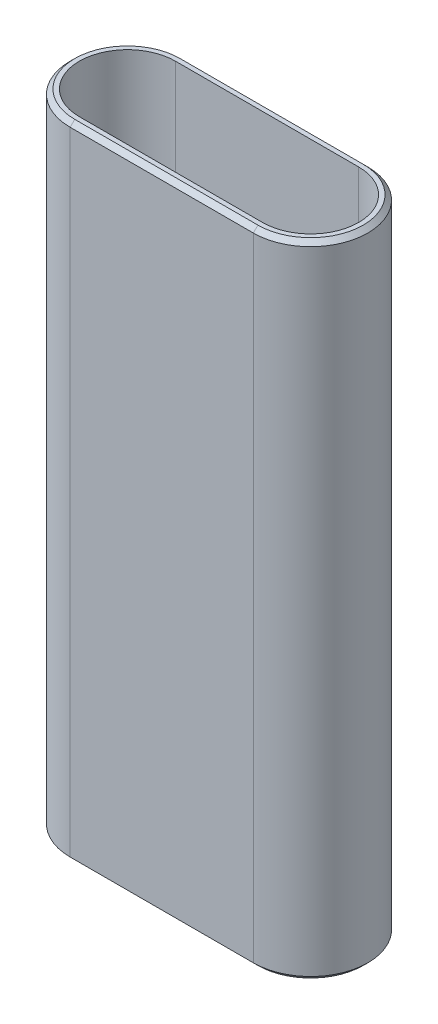
SolidWorks part; units mm, degrees
ref_plane "Front Plane" through (0, 0, 0) normal (0, 0, 1) x (1, 0, 0)
ref_plane "Top Plane" through (0, 0, 0) normal (0, 1, 0) x (1, 0, 0)
ref_plane "Right Plane" through (0, 0, 0) normal (1, 0, 0) x (0, 0, -1)
sketch "Sketch2" plane through (0, 12, 0) normal (0, -1, 0) x (1, 0, 0)
  line L8 (5.45, 3.45) -> (5.45, -3.45) construction
  line L9 (-7.45, -5.85) -> (7.45, -5.85)
  line L10 (-7.45, -5.85) -> (-7.45, 5.85)
  line L11 (-7.45, 5.85) -> (7.45, 5.85)
  line L12 (4.35, -3.85) -> (4.35, 3.85)
  line L13 (4.35, 3.85) -> (-4.35, 3.85)
  line L14 (-4.35, 3.85) -> (-4.35, -3.85)
  line L15 (-4.35, -3.85) -> (4.35, -3.85)
  line L16 (4.35, -3.85) -> (4.35, 3.85)
  line L17 (4.35, 3.85) -> (-4.35, 3.85)
  line L18 (-4.35, 3.85) -> (-4.35, -3.85)
  line L19 (-4.35, -3.85) -> (4.35, -3.85)
  line L20 (7.45, -5.85) -> (7.45, 5.85)
  line L21 (0, 5.85) -> (0, -5.85) construction
  line L22 (-7.45, 0) -> (7.45, 0) construction
  point P0 (0, 0)
  dimension "D2" = 2
  dimension "D3" = 2
  dimension "D1" = 0.4
extrude "Boss-Extrude1" add sketch "Sketch2" along normal offset from surface (12.6 mm away) 0.6 offset beyond the face yes
sketch "Sketch4" plane through (0, 0, 0) normal (1, 0, 0) x (0, 0, -1)
  line L1 (-1.6, 9.8) -> (-1.6, 8) construction
  line L2 (1.6, 8) -> (1.6, 9.8) construction
  line L3 (2.75, 8) -> (1.6, 8) construction
  line L4 (-1.6, 8) -> (-2.75, 8) construction
  line L5 (-2.75, 8) -> (-2.75, 12) construction
  line L6 (-2.75, 12) -> (-3.45, 12) construction
  line L7 (-3.45, 12) -> (-3.45, 0) construction
  line L8 (-3.45, 0) -> (3.45, 0) construction
  line L9 (3.45, 0) -> (3.45, 12) construction
  line L10 (3.45, 12) -> (2.75, 12) construction
  line L11 (2.75, 12) -> (2.75, 8) construction
  line L13 (-1.6, 9.8) -> (-1.6, 8) construction
  line L14 (1.6, 8) -> (1.6, 9.8) construction
  line L15 (2.75, 8) -> (1.6, 8) construction
  line L16 (-1.6, 8) -> (-2.75, 8) construction
  line L17 (-2.75, 8) -> (-2.75, 12) construction
  line L18 (-2.75, 12) -> (-3.45, 12) construction
  line L19 (-3.45, 12) -> (-3.45, 0) construction
  line L20 (-3.45, 0) -> (3.45, 0) construction
  line L21 (3.45, 0) -> (3.45, 12) construction
  line L22 (3.45, 12) -> (2.75, 12) construction
  line L23 (2.75, 12) -> (2.75, 8) construction
  line L24 (0, -990) -> (0, 49010) construction
  line L25 (-2.3, 10.25) -> (2.3, 10.25)
  line L26 (-2.3, 10.25) -> (-2.3, 7)
  line L27 (-2.3, 7) -> (2.3, 7)
  line L28 (1.6, 10) -> (-1.6, 10)
  line L29 (-1.6, 10) -> (-1.6, 9.8)
  line L30 (-1.6, 9.8) -> (1.6, 9.8)
  line L31 (1.6, 9.8) -> (1.6, 10)
  line L32 (1.6, 10) -> (-1.6, 10) construction
  line L33 (-1.6, 10) -> (-1.6, 9.8) construction
  line L34 (2.3, 10.25) -> (2.3, 7)
  line L35 (1.6, 9.8) -> (1.6, 10) construction
  point P20 (0, 10)
  dimension "D2" = 0.7
  dimension "D3" = 0.5
  dimension "D4" = 1
  dimension "D1" = 0
extrude "Cut-Extrude1" cut sketch "Sketch4" against normal through all both and the other way through all
sketch "Sketch5" plane through (0, -0.6, 0) normal (0, -1, 0) x (1, 0, 0)
  line L0 (-20, 0) -> (20, 0) construction
  line L1 (-20, 12.5) -> (20, 12.5)
  line L2 (-20, -12.5) -> (20, -12.5)
  arc A0 (-20, 12.5) -> (-20, -12.5) centre (-20, 0) ccw
  arc A1 (20, -12.5) -> (20, 12.5) centre (20, 0) ccw
  point P2 (0, 0)
  dimension "D1" = 25
  dimension "D2" = 40
extrude "Boss-Extrude2" add sketch "Sketch5" along normal blind 3
sketch "Sketch7" plane through (0, -0.6, 0) normal (0, 1, 0) x (1, 0, 0)
  line L0 (-20, -10.5) -> (20, -10.5)
  line L1 (20, 10.5) -> (-20, 10.5)
  line L2 (-20, -12.5) -> (20, -12.5)
  line L3 (20, 12.5) -> (-20, 12.5)
  line L4 (-20, -12.5) -> (20, -12.5)
  line L5 (20, 12.5) -> (-20, 12.5)
  arc A0 (20, -10.5) -> (20, 10.5) centre (20, 0) ccw
  arc A1 (-20, 10.5) -> (-20, -10.5) centre (-20, 0) ccw
  arc A2 (-20, 12.5) -> (-20, -12.5) centre (-20, 0) ccw
  arc A3 (20, -12.5) -> (20, 12.5) centre (20, 0) ccw
  arc A4 (-20, 12.5) -> (-20, -12.5) centre (-20, 0) ccw
  arc A5 (20, -12.5) -> (20, 12.5) centre (20, 0) ccw
  point P12 (22.5, 8)
  point P13 (22.5, 8)
  dimension "D1" = 0
  dimension "D2" = 2
extrude "Boss-Extrude3" add sketch "Sketch7" along normal blind 137
chamfer "Chamfer1" distance 1 angle 45 8 edges at (32.5, -3.6, 0) (0, -3.6, 12.5) (0, -3.6, -12.5) (-32.5, -3.6, 0) (32.5, 136.4, 0) (0, 136.4, -12.5) (0, 136.4, 12.5) (-32.5, 136.4, 0)
equation "\"case_length\"= 140"
equation "\"plate_thickness\"= 3"
equation "\"D1@Boss-Extrude2\"=\"plate_thickness\""
equation "\"D1@Boss-Extrude3\"=\"case_length\"-\"plate_thickness\""
equation "\"case_height\"= 25"
equation "\"case_width\"= 65"
equation "\"case_to_shell_offset\"= 19.6"
equation "\"body_tip_distance\"= 30"
equation "\"D2@Sketch5\"=\"case_width\"-\"case_height\""
equation "\"D1@Sketch5\"=\"case_height\""
